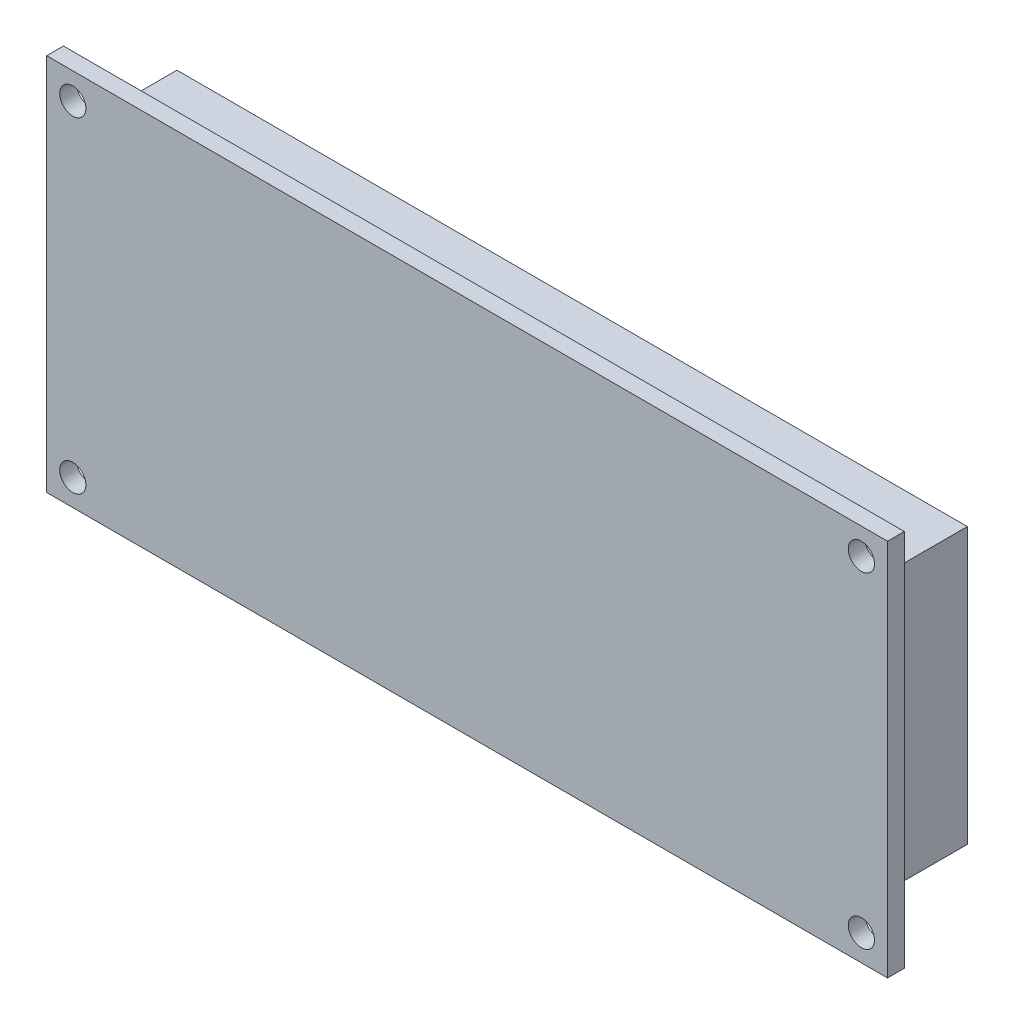
SolidWorks part; units mm, degrees
ref_plane "Front Plane" through (0, 0, 0) normal (0, 0, 1) x (1, 0, 0)
ref_plane "Top Plane" through (0, 0, 0) normal (0, 1, 0) x (1, 0, 0)
ref_plane "Right Plane" through (0, 0, 0) normal (1, 0, 0) x (0, 0, -1)
sketch "Sketch1" plane through (0, 0, 0) normal (0, 0, 1) x (1, 0, 0)
  line L1 (0, 0) -> (80.01, 0)
  line L2 (0, 0) -> (0, 35.9918)
  line L3 (0, 35.9918) -> (80.01, 35.9918)
  line L4 (80.01, 0) -> (80.01, 35.9918)
  line L5 (2.4892, 4.9022) -> (77.6986, 4.9022)
  line L6 (2.4892, 4.9022) -> (2.4892, 31.0896)
  line L7 (2.4892, 31.0896) -> (77.6986, 31.0896)
  line L8 (77.6986, 4.9022) -> (77.6986, 31.0896)
  dimension "D1" = 35.9918
  dimension "D2" = 80.01
  dimension "D3" = 2.4892
  dimension "D4" = 75.2094
  dimension "D5" = 26.1874
  dimension "D6" = 4.9022
extrude "Boss-Extrude1" add sketch "Sketch1" along normal blind 1.6002 contours L3 L4 L1 L2
extrude "Boss-Extrude2" add sketch "Sketch1<3>" against normal blind 8.3058 contours L7 L8 L5 L6
sketch "Sketch1<3>" plane through (0, 0, 0) normal (0, 0, 1) x (1, 0, 0) same geometry as "Sketch1"
sketch "Sketch2" plane through (0, 0, -8.3058) normal (0, 0, -1) x (-1, 0, 0)
  line L0 (-77.6986, 31.0896) -> (-2.4892, 4.9022)
  line L1 (-77.6986, 4.9022) -> (-2.4892, 31.0896)
  line L3 (-8.0899, 10.9982) -> (-72.0979, 10.9982)
  line L4 (-8.0899, 10.9982) -> (-8.0899, 24.9936)
  line L5 (-8.0899, 24.9936) -> (-72.0979, 24.9936)
  line L6 (-72.0979, 10.9982) -> (-72.0979, 24.9936)
  line L7 (-8.0899, 10.9982) -> (-72.0979, 24.9936) construction
  line L8 (-8.0899, 24.9936) -> (-72.0979, 10.9982) construction
  point P8 (-40.0939, 17.9959)
  point P9 (-40.0939, 17.9959)
  dimension "D1" = 13.9954
  dimension "D2" = 64.008
extrude "Cut-Extrude1" cut sketch "Sketch2" against normal blind 0.254 contours L5 L6 L3 L4
sketch "Sketch3" plane through (0, 0, 0) normal (0, 0, -1) x (-1, 0, 0)
  line L0 (-80.01, 0) -> (-80.01, 35.9918) construction
  line L1 (0, 0) -> (-80.01, 0) construction
  line L2 (0, 35.9918) -> (-80.01, 35.9918) construction
  line L3 (0, 0) -> (0, 35.9918) construction
  circle A0 centre (-77.5208, 2.4892) radius 1.2446
  circle A1 centre (-77.5208, 33.5026) radius 1.2446
  circle A2 centre (-2.4892, 33.5026) radius 1.2446
  circle A3 centre (-2.4892, 2.4892) radius 1.2446
  dimension "D1" = 2.4892
  dimension "D4" = 2.4892
  dimension "D5" = 2.4892
  dimension "D6" = 2.4892
  dimension "D2" = 2.4892
  dimension "D3" = 2.4892
  dimension "D7" = 2.4892
  dimension "D8" = 2.4892
  dimension "D9" = 2.4892
  dimension "D10" = 2.4892
  dimension "D11" = 2.4892
  dimension "D12" = 2.4892
extrude "Cut-Extrude2" cut sketch "Sketch3" against normal blind 2.54
